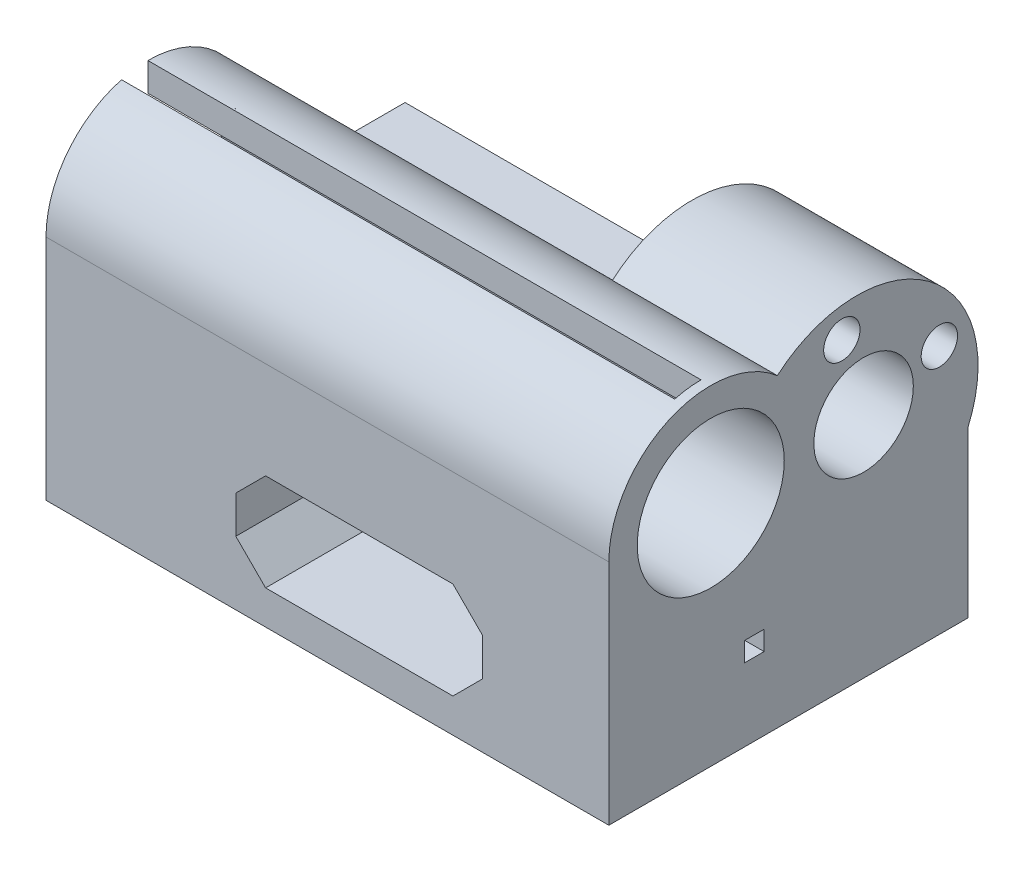
SolidWorks part; units mm, degrees
ref_plane "Front Plane" through (0, 0, 0) normal (0, 0, 1) x (1, 0, 0)
ref_plane "Top Plane" through (0, 0, 0) normal (0, 1, 0) x (1, 0, 0)
ref_plane "Right Plane" through (0, 0, 0) normal (1, 0, 0) x (0, 0, -1)
sketch "Sketch2" plane through (0, 0, 0) normal (0, 1, 0) x (1, 0, 0)
  line L1 (-29, -18.5) -> (29, -18.5)
  line L2 (-29, -18.5) -> (-29, 18.5)
  line L3 (-29, 18.5) -> (29, 18.5)
  line L4 (29, -18.5) -> (29, 18.5)
  line L5 (-29, -18.5) -> (29, 18.5) construction
  line L6 (-29, 18.5) -> (29, -18.5) construction
  point P0 (0, 0)
  dimension "D1" = 58
  dimension "D2" = 37
extrude "Boss-Extrude1" add sketch "Sketch2" along normal blind 17
sketch "Sketch3" plane through (29, 0, 0) normal (1, 0, 0) x (0, 0, -1)
  line L0 (-18.5, 0) -> (18.5, 0) construction
  line L1 (-18.5, 23.5) -> (-18.5, 17)
  line L2 (-18.5, 17) -> (-18.5, 0) construction
  line L5 (2.5, 23.5) -> (2.5, 17)
  line L6 (-18.5, 17) -> (18.5, 17) construction
  line L7 (-18.5, 17) -> (2.5, 17)
  arc A0 (2.5, 23.5) -> (-18.5, 23.5) centre (-8, 23.5) ccw
  dimension "D2" = 21
  dimension "D4" = 23.5
  dimension "D5" = 10.5
extrude "Boss-Extrude2" add sketch "Sketch3" against normal up to surface (58 mm away) up to face at (-29, 8.5, 0)
sketch "Sketch4" plane through (29, 0, 0) normal (1, 0, 0) x (0, 0, -1)
  line L1 (-18.5, 0) -> (18.5, 0) construction
  circle A0 centre (7.0436, 22) radius 12.5
  dimension "D1" = 25
  dimension "D2" = 22
extrude "Boss-Extrude3" add sketch "Sketch4" against normal blind 17
sketch "Sketch5" plane through (0, 0, -18.5) normal (0, 0, -1) x (-1, 0, 0)
  line L0 (-16, 6.57) -> (-16, 10.427)
  line L1 (-16, 10.427) -> (-12.93, 13.497)
  line L2 (-12.93, 13.497) -> (6.37, 13.497)
  line L3 (6.37, 13.497) -> (9.44, 10.427)
  line L4 (9.44, 10.427) -> (9.44, 6.57)
  line L5 (9.44, 6.57) -> (6.37, 3.5)
  line L6 (6.37, 3.5) -> (-12.93, 3.5)
  line L7 (-12.93, 3.5) -> (-16, 6.57)
  line L8 (-29, 0) -> (29, 0) construction
  line L9 (-29, 17) -> (-29, 0) construction
  dimension "D1" = 3.857
  dimension "D2" = 3.857
  dimension "D3" = 135
  dimension "D4" = 135
  dimension "D5" = 3.07
  dimension "D6" = 3.07
  dimension "D7" = 3.07
  dimension "D8" = 3.07
  dimension "D9" = 19.3
  dimension "D10" = 3.5
  dimension "D11" = 13
extrude "Cut-Extrude1" cut sketch "Sketch5" against normal through all
sketch "Sketch6" plane through (0, 0, -18.5) normal (0, 0, -1) x (-1, 0, 0)
  line L0 (-29, 0) -> (29, 0) construction
  line L1 (-29, 17) -> (-29, 0) construction
  circle A0 centre (-23, 8.5) radius 4.076
  circle A1 centre (22, 8.5) radius 4.076
  dimension "D5" = 8.152
  dimension "D6" = 8.152
  dimension "D1" = 8.5
  dimension "D2" = 8.5
  dimension "D3" = 6
  dimension "D4" = 51
extrude "Cut-Extrude2" cut sketch "Sketch6" against normal blind 23
sketch "Sketch7" plane through (29, 0, 0) normal (1, 0, 0) x (0, 0, -1)
  line L0 (-18.5, 23.5) -> (-18.5, 0) construction
  line L1 (-18.5, 0) -> (18.5, 0) construction
  circle A0 centre (-8, 23.5) radius 7.575
  circle A1 centre (7.7501, 23.5) radius 5.125
  dimension "D1" = 10.25
  dimension "D2" = 15.15
  dimension "D3" = 26.2501
  dimension "D4" = 23.5
extrude "Cut-Extrude3" cut sketch "Sketch7" against normal through all
sketch "Sketch8" plane through (29, 0, 0) normal (1, 0, 0) x (0, 0, -1)
  line L0 (7.7501, 23.5) -> (5.5097, 31.31) construction
  line L3 (7.7501, 23.5) -> (15.5601, 25.7405) construction
  line L4 (5.5097, 31.31) -> (6.0267, 29.5077) construction
  line L7 (15.5601, 25.7405) -> (13.7578, 25.2235) construction
  circle A1 centre (5.5097, 31.31) radius 1.875
  circle A2 centre (15.5601, 25.7405) radius 1.875
  dimension "D1" = 3.75
  dimension "D2" = 6.25
  dimension "D3" = 3.75
  dimension "D7" = 6.25
extrude "Cut-Extrude4" cut sketch "Sketch8" against normal through all
sketch "Sketch12" plane through (-29, 0, 0) normal (-1, 0, 0) x (0, 0, 1)
  line L0 (-18.5, 17) -> (-18.5, 0) construction
  line L1 (4.5, 7.5) -> (2.5, 7.5)
  line L2 (4.5, 7.5) -> (4.5, 9.5)
  line L3 (4.5, 9.5) -> (2.5, 9.5)
  line L4 (2.5, 7.5) -> (2.5, 9.5)
  line L5 (-18.5, 0) -> (18.5, 0) construction
  dimension "D1" = 23
  dimension "D2" = 2
  dimension "D3" = 2
  dimension "D4" = 7.5
extrude "Cut-Extrude6" cut sketch "Sketch12" against normal blind 8
mirror "Mirror1" about plane through (0, 0, 0) normal (1, 0, 0) of "Cut-Extrude6"
sketch "Sketch13" plane through (-29, 0, 0) normal (-1, 0, 0) x (0, 0, 1)
  line L0 (8, 23.5) -> (10.7176, 33.6422) construction
  line L1 (8, 23.5) -> (-2.5, 23.5) construction
  line L2 (8, 23.5) -> (8, 34) construction
  line L3 (9.9606, 30.8169) -> (10.7176, 33.6422)
  line L4 (8, 34) -> (8, 31.075)
  arc A0 (9.9606, 30.8169) -> (8, 31.075) centre (8, 23.5) ccw
  arc A1 (-2.5, 23.5) -> (8, 34) centre (8, 23.5) ccw
  arc A2 (18.5, 23.5) -> (-2.5, 23.5) centre (8, 23.5) ccw construction
  arc A3 (1.1397, 31.449) -> (-2.5, 23.5) centre (8, 23.5) ccw construction
  circle A4 centre (8, 23.5) radius 7.575 construction
  circle M5 centre (8, 23.5) radius 7.575
  arc M8 (18.5, 23.5) -> (-2.5, 23.5) centre (8, 23.5) ccw
  dimension "D1" = 15
  dimension "D2" = 90
extrude "Cut-Extrude7" cut sketch "Sketch13" against normal blind 57 contours L4 L3 M8 M5 region at (-29, 32.5126, 9.1865)
sketch "Sketch14" plane through (0, 0, 0) normal (0, -1, 0) x (1, 0, 0)
  line L0 (2.058, -11.5) -> (29, -11.5) construction
  line L1 (29, 18.5) -> (29, -18.5) construction
  line L2 (2.058, -11.5) -> (2.058, -18.5) construction
  line L3 (29, -18.5) -> (-29, -18.5) construction
  circle A0 centre (2.058, -11.5) radius 1.5
  dimension "D1" = 3
  dimension "D2" = 7
  dimension "D3" = 26.942
extrude "Cut-Extrude8" cut sketch "Sketch14" against normal through all
